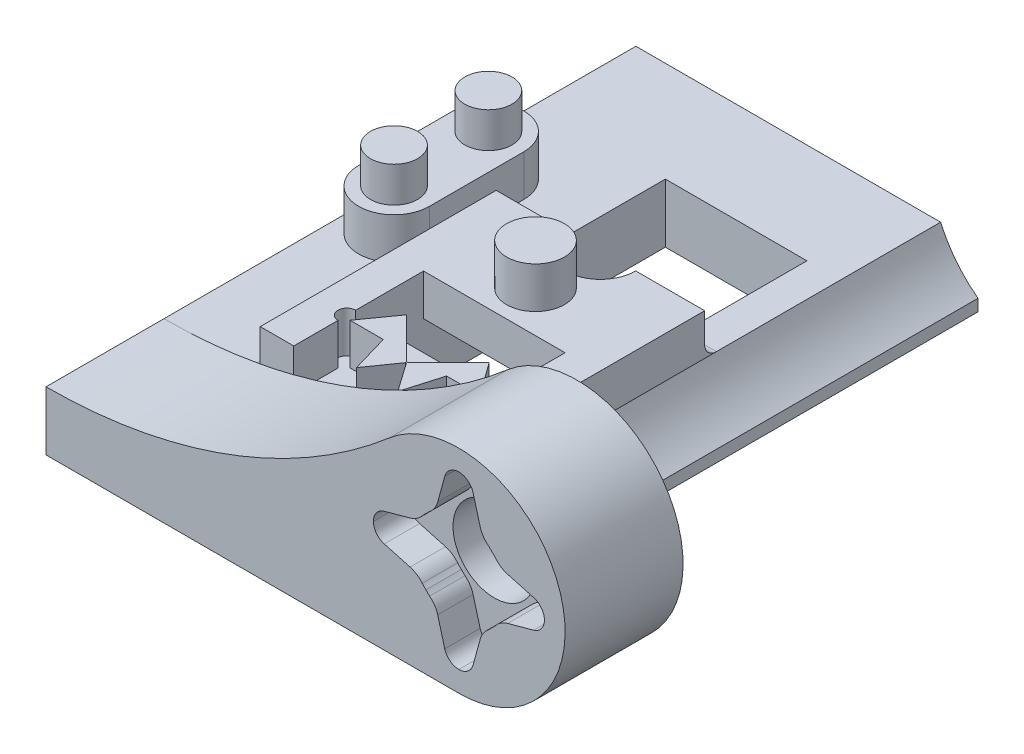
SolidWorks part; units mm, degrees
ref_plane "Front Plane" through (0, 0, 0) normal (0, 0, 1) x (1, 0, 0)
ref_plane "Top Plane" through (0, 0, 0) normal (0, 1, 0) x (1, 0, 0)
ref_plane "Right Plane" through (0, 0, 0) normal (1, 0, 0) x (0, 0, -1)
sketch "Sketch1" plane through (0, 0, 0) normal (0, 0, 1) x (1, 0, 0)
  line L0 (0, -9) -> (-35, -9)
  line L1 (-35, -9) -> (-35, -4)
  circle A0 centre (0, 0) radius 9
  arc A1 (-35, -4) -> (-5.8726, 6.82) centre (-35.0202, 40.6697) ccw
  dimension "D1" = 18
  dimension "D2" = 5
  dimension "D3" = 35
  dimension "D4" = 10.82
extrude "Boss-Extrude1" add sketch "Sketch1" along normal mid plane 10 contours A0 | A1 L1 L0 A0 region at (-18.5529, -4.8443, 0) region at (0, 0, 0)
sketch "Sketch2" plane through (0, 0, -5) normal (0, 0, -1) x (-1, 0, 0)
  circle A0 centre (0, 0) radius 7
  dimension "D1" = 14
extrude "Boss-Extrude2" add sketch "Sketch2" along normal mid plane 3 draft 30
sketch "Sketch3" plane through (0, 0, 5) normal (0, 0, 1) x (1, 0, 0)
  line L0 (0, 7.25) -> (0, -7.25) construction
  line L1 (1.2, -6.33) -> (1.8, -4.1378)
  line L2 (0, 0) -> (11.2055, 0) construction
  line L3 (0, 0) -> (7.1307, -7.1307) construction
  line L4 (6.33, -1.2) -> (4.1378, -1.8)
  line L5 (0, 0) -> (7.1307, 7.1307) construction
  line L6 (6.33, 1.2) -> (4.1378, 1.8)
  line L7 (1.2, 6.33) -> (1.8, 4.1378)
  line L8 (0, 0) -> (-7.1307, 7.1307) construction
  line L9 (0, 0) -> (-7.1307, -7.1307) construction
  line L10 (-1.2, 6.33) -> (-1.8, 4.1378)
  line L11 (-6.33, 1.2) -> (-4.1378, 1.8)
  line L12 (-6.33, -1.2) -> (-4.1378, -1.8)
  line L13 (-1.2, -6.33) -> (-1.8, -4.1378)
  arc A0 (0, -7.25) -> (1.2, -6.33) centre (-0.0057, -6) ccw
  arc A1 (1.8, -4.1378) -> (2.48, -3.1078) centre (3.7276, -4.671) cw
  arc A2 (2.48, -3.1078) -> (2.7942, -2.7942) centre (-0.1839, -0.1239) ccw
  arc A3 (3.1078, -2.48) -> (2.7942, -2.7942) centre (0.1239, 0.1839) cw
  arc A4 (4.1378, -1.8) -> (3.1078, -2.48) centre (4.671, -3.7276) ccw
  arc A5 (7.25, 0) -> (6.33, -1.2) centre (6, 0.0057) cw
  arc A6 (7.25, 0) -> (6.33, 1.2) centre (6, -0.0057) ccw
  arc A7 (4.1378, 1.8) -> (3.1078, 2.48) centre (4.671, 3.7276) cw
  arc A8 (3.1078, 2.48) -> (2.7942, 2.7942) centre (0.1239, -0.1839) ccw
  arc A9 (2.48, 3.1078) -> (2.7942, 2.7942) centre (-0.1839, 0.1239) cw
  arc A10 (1.8, 4.1378) -> (2.48, 3.1078) centre (3.7276, 4.671) ccw
  arc A11 (0, 7.25) -> (1.2, 6.33) centre (-0.0057, 6) cw
  arc A12 (0, 7.25) -> (-1.2, 6.33) centre (0.0057, 6) ccw
  arc A13 (-1.8, 4.1378) -> (-2.48, 3.1078) centre (-3.7276, 4.671) cw
  arc A14 (-2.48, 3.1078) -> (-2.7942, 2.7942) centre (0.1839, 0.1239) ccw
  arc A15 (-3.1078, 2.48) -> (-2.7942, 2.7942) centre (-0.1239, -0.1839) cw
  arc A16 (-4.1378, 1.8) -> (-3.1078, 2.48) centre (-4.671, 3.7276) ccw
  arc A17 (-7.25, 0) -> (-6.33, 1.2) centre (-6, -0.0057) cw
  arc A18 (-7.25, 0) -> (-6.33, -1.2) centre (-6, 0.0057) ccw
  arc A19 (-4.1378, -1.8) -> (-3.1078, -2.48) centre (-4.671, -3.7276) cw
  arc A20 (-3.1078, -2.48) -> (-2.7942, -2.7942) centre (-0.1239, 0.1839) ccw
  arc A21 (-2.48, -3.1078) -> (-2.7942, -2.7942) centre (0.1839, -0.1239) cw
  arc A22 (-1.8, -4.1378) -> (-2.48, -3.1078) centre (-3.7276, -4.671) ccw
  arc A23 (0, -7.25) -> (-1.2, -6.33) centre (0.0057, -6) cw
  point P5 (0, 0)
  point P11 (0, 0)
  dimension "D2" = 1.25
  dimension "D6" = 2
  dimension "D9" = 4
  dimension "D1" = 14.5
  dimension "D3" = 0.92
  dimension "D4" = 1.2
  dimension "D5" = 0.6
  dimension "D7" = 1.03
  dimension "D8" = 0.68
  dimension "D12" = 45
extrude "Cut-Extrude1" cut sketch "Sketch3" against normal blind 3
sketch "Sketch4" plane through (0, 0, -5) normal (0, 0, -1) x (-1, 0, 0)
  line L0 (35, -9) -> (35, -4)
  line L1 (35, -4) -> (9.17, -4)
  line L2 (35, -9) -> (6, -9)
  line L3 (0, -9) -> (35, -9) construction
  line L4 (6, -9) -> (6, -8)
  arc A0 (9.17, -4) -> (6, -8) centre (0.0072, 0.0054) cw
  dimension "D4" = 10
  dimension "D1" = 29
  dimension "D2" = 25.83
  dimension "D3" = 1
extrude "Boss-Extrude3" add sketch "Sketch4" along normal blind 40
sketch "Sketch5" plane through (0, -4, 0) normal (0, 1, 0) x (1, 0, 0)
  line L0 (-9.17, 45) -> (-9.17, 5) construction
  line L1 (-24, 36.5) -> (-12, 36.5)
  line L2 (-24, 36.5) -> (-24, 13.5)
  line L3 (-24, 13.5) -> (-12, 13.5)
  line L4 (-12, 36.5) -> (-12, 13.5)
  line L5 (-35, 45) -> (-9.17, 45) construction
  dimension "D1" = 12
  dimension "D2" = 23
  dimension "D3" = 2.83
  dimension "D4" = 8.5
extrude "Cut-Extrude2" cut sketch "Sketch5" against normal blind 40
sketch "Sketch6" plane through (0, -4, 0) normal (0, 1, 0) x (1, 0, 0)
  line L0 (-12, 25) -> (-51, 25) construction
  line L1 (-12, 13.5) -> (-12, 36.5) construction
  line L2 (-31.5, 29) -> (-31.5, 21) construction
  line L3 (-28.5, 29) -> (-28.5, 21)
  line L4 (-34.5, 29) -> (-34.5, 21)
  line L5 (-35, 45) -> (-35, 5) construction
  arc A0 (-28.5, 29) -> (-34.5, 29) centre (-31.5, 29) ccw
  arc A1 (-34.5, 21) -> (-28.5, 21) centre (-31.5, 21) ccw
  point P6 (-31.5, 25)
  dimension "D1" = 3
  dimension "D2" = 0.5
  dimension "D3" = 8
extrude "Boss-Extrude4" add sketch "Sketch6" along normal blind 3.5
sketch "Sketch7" plane through (0, -0.5, 0) normal (0, 1, 0) x (1, 0, 0)
  line L0 (-28.5, 25) -> (-34.5, 25) construction
  line L1 (-28.5, 21) -> (-28.5, 29) construction
  line L2 (-34.5, 29) -> (-34.5, 21) construction
  line L3 (-31.5, 25) -> (-31.5, 29)
  circle A0 centre (-31.5, 29) radius 2
  circle A1 centre (-31.5, 21) radius 2
  dimension "D2" = 4
  dimension "D1" = 4
extrude "Boss-Extrude5" add sketch "Sketch7" along normal blind 3 contours A0 | A1 region at (-30.1258, -0.5, -27.6258) region at (-31.5, -0.5, -21)
sketch "Sketch8" plane through (0, 0, -6.5) normal (0, 0, -1) x (-1, 0, 0)
  circle A0 centre (0, 0) radius 3.5
  dimension "D1" = 7
extrude "Cut-Extrude3" cut sketch "Sketch8" against normal through all
sketch "Sketch9" plane through (0, -4, 0) normal (0, 1, 0) x (1, 0, 0)
  line L0 (-26.84, 5) -> (-26.84, 25)
  line L1 (-35, 5) -> (-9.17, 5) construction
  line L2 (-26.84, 25) -> (-21.01, 25)
  line L3 (-15.01, 25) -> (-9.17, 25)
  line L4 (-9.17, 45) -> (-9.17, 5) construction
  line L5 (-21.01, 25) -> (-15.01, 25) construction
  line L6 (-26.84, 5) -> (-24, 5)
  line L7 (-9.17, 5) -> (-9.17, 25)
  line L8 (-24, 8.75) -> (-24, 5)
  line L9 (-24, 36.5) -> (-24, 13.5) construction
  line L10 (-24, 8.75) -> (-24, 10.25) construction
  line L11 (-24, 10.25) -> (-24, 16)
  line L12 (-24, 16) -> (-18.01, 16)
  line L13 (-18, 13.5) -> (-18, 20.7385) construction
  line L14 (-24, 13.5) -> (-12, 13.5) construction
  line L15 (-12, 8.75) -> (-12, 5)
  line L16 (-12, 10.25) -> (-12, 16)
  line L17 (-12, 16) -> (-17.99, 16)
  line L18 (-12, 5) -> (-9.17, 5)
  line L19 (-17.99, 16) -> (-18.01, 16)
  arc A0 (-21.01, 25) -> (-15.01, 25) centre (-18.01, 25) ccw
  arc A1 (-24, 10.25) -> (-24, 8.75) centre (-24, 9.5) ccw
  arc A2 (-12, 10.25) -> (-12, 8.75) centre (-12, 9.5) cw
  dimension "D4" = 6
  dimension "D7" = 0.75
  dimension "D1" = 20
  dimension "D2" = 17.67
  dimension "D3" = 5.83
  dimension "D5" = 3.75
  dimension "D6" = 11
extrude "Boss-Extrude6" add sketch "Sketch9" along normal blind 3.5
sketch "Sketch10" plane through (0, -0.5, 0) normal (0, 1, 0) x (1, 0, 0)
  line L0 (-18.01, 22) -> (-18, 16) construction
  line L1 (-24, 16) -> (-12, 16) construction
  arc A0 (-21.01, 25) -> (-15.01, 25) centre (-18.01, 25) ccw construction
  circle A1 centre (-18.0058, 19.5) radius 2.45
  dimension "D1" = 4.9
  dimension "D2" = 2.5
extrude "Boss-Extrude7" add sketch "Sketch10" along normal blind 3.5
sketch "Sketch11" plane through (0, -4, 0) normal (0, 1, 0) x (1, 0, 0)
  line L0 (-26.84, 9.2709) -> (-9.17, 9.2709) construction
  line L1 (-26.84, 25) -> (-26.84, 5) construction
  line L2 (-9.17, 5) -> (-9.17, 25) construction
  line L3 (-18, 13.5) -> (-18, 5) construction
  line L4 (-24, 13.5) -> (-12, 13.5) construction
  line L5 (-24, 5) -> (-12, 5) construction
  line L6 (-20.68, 9.2709) -> (-23.5, 9.2709)
  line L7 (-23.5, 9.2709) -> (-21.5, 12.0709)
  line L8 (-20.68, 9.2709) -> (-19.75, 6.0709)
  line L9 (-19.75, 6.0709) -> (-18.03, 8.5209)
  line L10 (-18.03, 8.5209) -> (-17.97, 8.5209)
  line L11 (-21.5, 12.0709) -> (-18.05, 8.6209)
  line L12 (-18.05, 8.6209) -> (-18, 8.6209)
  line L13 (-17.95, 8.6209) -> (-18, 8.6209)
  line L14 (-14.5, 12.0709) -> (-17.95, 8.6209)
  line L15 (-16.25, 6.0709) -> (-17.97, 8.5209)
  line L16 (-15.32, 9.2709) -> (-16.25, 6.0709)
  line L17 (-12.5, 9.2709) -> (-14.5, 12.0709)
  line L18 (-15.32, 9.2709) -> (-12.5, 9.2709)
  point P14 (-18.025, 8.6209)
  point P24 (-18, 8.5209)
  dimension "D1" = 2.82
  dimension "D2" = 2
  dimension "D3" = 3.5
  dimension "D4" = 0.93
  dimension "D5" = 1.72
  dimension "D6" = 0.1
  dimension "D7" = 0.05
  dimension "D8" = 3.45
  dimension "D9" = 3.2
  dimension "D10" = 2.8
extrude "Boss-Extrude8" add sketch "Sketch11" along normal blind 3.5
fillet "Fillet1" radius 1 3 edges at (-10.585, -4, -25) (-25.42, -4, -25) (-26.84, -4, -15)
